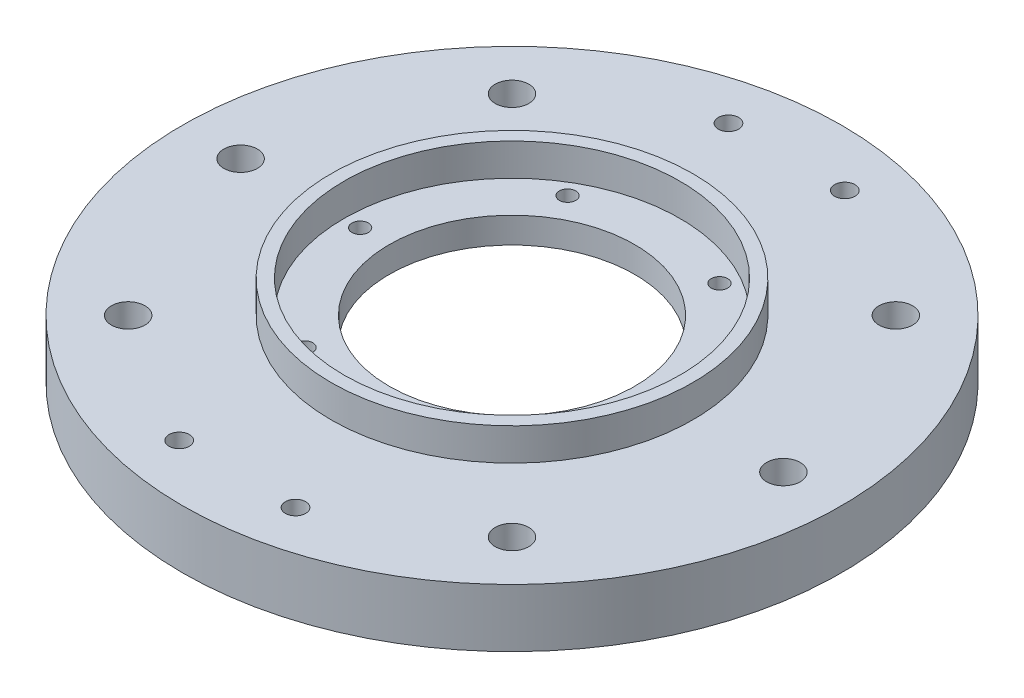
SolidWorks part; units mm, degrees
material "1060 Сплав"
ref_plane "Спереди" through (0, 0, 0) normal (0, 0, 1) x (1, 0, 0)
ref_plane "Сверху" through (0, 0, 0) normal (0, 1, 0) x (1, 0, 0)
ref_plane "Справа" through (0, 0, 0) normal (1, 0, 0) x (0, 0, -1)
sketch "Эскиз1" plane through (0, 0, 0) normal (0, 1, 0) x (1, 0, 0)
  circle A0 centre (0, 0) radius 19
  circle A1 centre (0, 0) radius 51
  dimension "D1" = 38
  dimension "D2" = 102
extrude "Бобышка-Вытянуть1" add sketch "Эскиз1" along normal blind 4
hole_wizard "Сверло под метчик  спиральное M2.51" positions "Эскиз2" profile "Эскиз3" hole size "M2.5x0.45" standard "DIN"
sketch "Эскиз2" plane through (0, 4, 0) normal (0, 1, 0) x (1, 0, 0)
  point P0 (23.5, 0)
  dimension "D1" = 23.5
sketch "Эскиз3" plane through (23.5, 4, 0) normal (1, 0, 0) x (0, 0, 1)
  line L0 (0, 0) -> (0, 8.7661)
  line L1 (0, 8.7661) -> (1.275, 8)
  line L2 (1.275, 8) -> (1.275, 0)
  line L5 (1.275, 0) -> (0, 0)
  line L10 (0, 8.7661) -> (-1.275, 8) construction
  line L11 (0, -6.35) -> (0, 107.95) construction
  dimension "Диаметр отверстия" = 2.55
  dimension "Глубина отверстия" = 8
  dimension "Угол заточки сверла" = 118
pattern_circular "Круговой массив1" count 6 over 360 about axis through (0, 4, 0) along (0, 1, 0) of "Сверло под метчик  спиральное M2.51"
hole_wizard "Сверло под метчик  спиральное M32" positions "Эскиз4" profile "Эскиз5" hole size "M3x0.5" standard "DIN" end condition through all
sketch "Эскиз4" plane through (0, 0, 0) normal (0, -1, 0) x (-1, 0, 0)
  point P0 (-9, -42.5)
  dimension "D1" = 9
  dimension "D2" = 42.5
sketch "Эскиз5" plane through (9, 0, 42.5) normal (1, 0, 0) x (0, 0, -1)
  line L0 (0, 0) -> (0, 4)
  line L1 (0, 4) -> (1.575, 4)
  line L2 (1.575, 4) -> (1.575, 0)
  line L5 (1.575, 0) -> (0, 0)
  line L11 (0, -6.35) -> (0, 107.95) construction
  dimension "Диаметр сквозного отверстия" = 3.15
  dimension "Глубина сквозного отверстия" = 4
sketch "Эскиз6" plane through (0, 0, 0) normal (0, 1, 0) x (1, 0, 0)
  line L0 (0, 0) -> (0, 15.2777) construction
  line L1 (0, 0) -> (-12.2514, 0) construction
pattern_linear "Линейный массив1" count 2 spacing 18 along (-1, 0, 0) count 2 spacing 85 along (0, 0, -1) of "Сверло под метчик  спиральное M32"
hole_wizard "Сверло под метчик  спиральное M52" positions "Эскиз11" profile "Эскиз12" hole size "M5x0.8" standard "DIN" end condition through all
sketch "Эскиз11" plane through (0, 0, 0) normal (0, -1, 0) x (-1, 0, 0)
  point P0 (42, 0)
  point P2 (-42, 0)
  dimension "D1" = 42
  dimension "D2" = 42
sketch "Эскиз12" plane through (-42, 0, 0) normal (1, 0, 0) x (0, 0, -1)
  line L0 (0, 0) -> (0, 4)
  line L1 (0, 4) -> (2.6, 4)
  line L2 (2.6, 4) -> (2.6, 0)
  line L5 (2.6, 0) -> (0, 0)
  line L11 (0, -6.35) -> (0, 107.95) construction
  dimension "Диаметр сквозного отверстия" = 5.2
  dimension "Глубина сквозного отверстия" = 4
pattern_circular "Круговой массив3" count 2 every 45 about axis through (0, 0, 0) along (0, 1, 0) of "Сверло под метчик  спиральное M52" other way count 2
sketch "Эскиз14" plane through (0, 4, 0) normal (0, 1, 0) x (1, 0, 0)
  circle A0 centre (0, 0) radius 26
  circle A1 centre (0, 0) radius 28
  dimension "D1" = 52
  dimension "D2" = 56
extrude "Бобышка-Вытянуть2" add sketch "Эскиз14" along normal blind 5
sketch "Эскиз15" plane through (0, 0, 0) normal (0, -1, 0) x (1, 0, 0)
  circle A0 centre (0, 0) radius 51
  circle A1 centre (0, 0) radius 48
  dimension "D1" = 102
  dimension "D2" = 96
extrude "Бобышка-Вытянуть3" add sketch "Эскиз15" along normal blind 5
